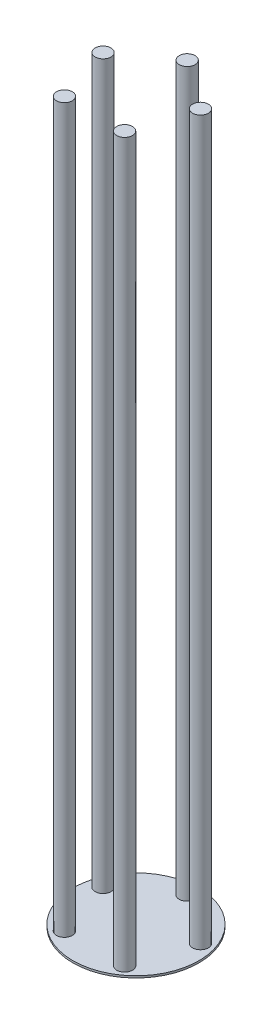
SolidWorks part; units mm, degrees
ref_plane "Front Plane" through (0, 0, 0) normal (0, 0, 1) x (1, 0, 0)
ref_plane "Top Plane" through (0, 0, 0) normal (0, 1, 0) x (1, 0, 0)
ref_plane "Right Plane" through (0, 0, 0) normal (1, 0, 0) x (0, 0, -1)
sketch "Sketch1" plane through (0, 0, 0) normal (0, 1, 0) x (1, 0, 0)
  circle A0 centre (0, 0) radius 101.6
extrude "Boss-Extrude1" add sketch "Sketch1" along normal blind 3.175
sketch "Sketch2" plane through (0, 3.175, 0) normal (0, 1, 0) x (1, 0, 0)
  circle A0 centre (0, 82.55) radius 12.827
  circle A1 centre (78.5097, 25.5094) radius 12.827
  circle A2 centre (48.5217, -66.7844) radius 12.827
  circle A3 centre (-48.5217, -66.7844) radius 12.827
  circle A4 centre (-78.5097, 25.5094) radius 12.827
  point P13 (0, 0)
  dimension "D1" = 82.55
  dimension "D2" = 25.654
  dimension "D3" = 5
extrude "Cut-Extrude2" cut sketch "Sketch2" against normal blind 3.175
sketch "Sketch3" plane through (0, 0, 0) normal (0, 1, 0) x (1, 0, 0)
  circle A0 centre (0, 82.55) radius 12.7
  circle A1 centre (78.5097, 25.5094) radius 12.7
  circle A2 centre (48.5217, -66.7844) radius 12.7
  circle A3 centre (-48.5217, -66.7844) radius 12.7
  circle A4 centre (-78.5097, 25.5094) radius 12.7
  point P13 (0, 0)
  dimension "D1" = 25.4
  dimension "D2" = 5
extrude "Boss-Extrude3" add sketch "Sketch3" along normal blind 1168.4
sketch "Sketch5" plane through (0, 1168.4, 0) normal (0, 1, 0) x (1, 0, 0)
  circle A1 centre (0, 0) radius 101.6
  dimension "D1" = 203.2
